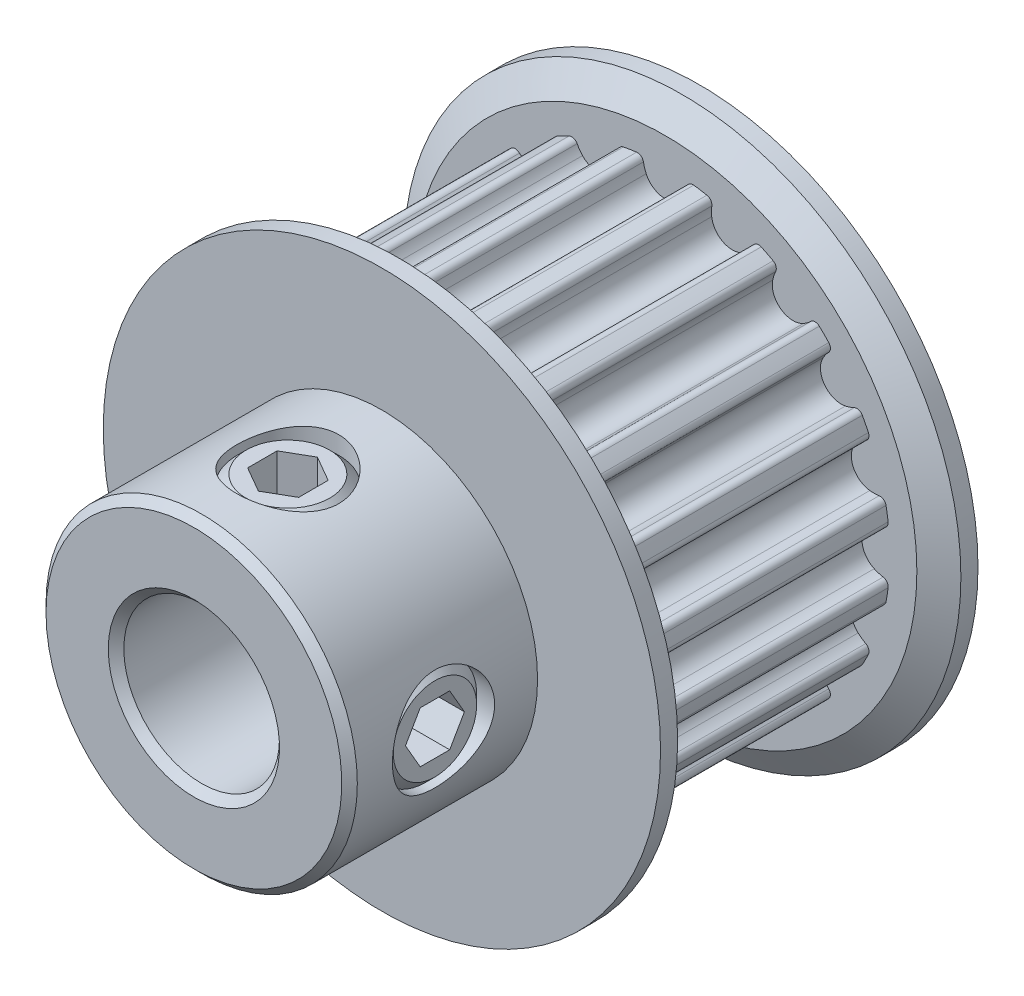
SolidWorks part; units mm, degrees
ref_plane "Front Plane" through (0, 0, 0) normal (0, 0, 1) x (1, 0, 0)
ref_plane "Top Plane" through (0, 0, 0) normal (0, 1, 0) x (1, 0, 0)
ref_plane "Right Plane" through (0, 0, 0) normal (1, 0, 0) x (0, 0, -1)
sketch "Sketch1" plane through (0, 0, 0) normal (0, 0, 1) x (1, 0, 0)
  line L1 (-2.6202, 8.0295) -> (2.6202, 8.0295) construction
  line L4 (0, 0) -> (0, 8.0295) construction
  line L5 (0, 8.0295) -> (0, 13.1511) construction
  line L6 (0, 9.5505) -> (2.9628, 9.0793) construction
  line L7 (2.9628, 9.0793) -> (4.0126, 8.7367) construction
  line L8 (2.9628, 9.0793) -> (2.6202, 8.0295) construction
  line L9 (-2.9628, 9.0793) -> (-2.6202, 8.0295) construction
  line L10 (-2.8446, 8.7171) -> (-3.7091, 11.3665)
  line L11 (-3.7091, 11.3665) -> (3.7091, 11.3665)
  line L12 (3.7091, 11.3665) -> (2.8446, 8.7171)
  circle A0 centre (0, 0) radius 9.5505 construction
  circle A1 centre (0, 0) radius 11.3665 construction
  circle A2 centre (0, 0) radius 9.1695 construction
  arc A3 (-0.7739, 8.5279) -> (0.7739, 8.5279) centre (0, 8.8795) ccw
  arc A4 (-0.7739, 8.5279) -> (-0.8866, 8.891) centre (0.61, 9.1566) cw
  arc A5 (-2.8446, 8.7171) -> (-1.1645, 9.0953) centre (0, 0) cw
  arc A6 (-0.8866, 8.891) -> (-1.1645, 9.0953) centre (-1.1328, 8.8473) ccw
  arc A7 (2.8446, 8.7171) -> (1.1645, 9.0953) centre (0, 0) ccw
  arc A8 (0.8866, 8.891) -> (1.1645, 9.0953) centre (1.1328, 8.8473) cw
  arc A9 (0.7739, 8.5279) -> (0.8866, 8.891) centre (-0.61, 9.1566) ccw
  point P6 (0, 20.9083)
  point P11 (0, 9.5505)
  point P13 (0, 11.3665)
  point P14 (0, 9.1695)
  dimension "D1" = 7.7573
  dimension "D2" = 3.6006
sketch "Sketch2" plane through (0, 0, 0) normal (1, 0, 0) x (0, 0, -1)
  line L0 (-10.31, 3.175) -> (10.31, 3.175)
  line L1 (-10.31, 3.175) -> (-10.31, 6.35)
  line L2 (-10.31, 6.35) -> (-2.64, 6.35)
  line L3 (-2.64, 6.35) -> (-2.64, 11.3665)
  line L4 (-2.64, 11.3665) -> (-1.245, 11.3665) construction
  line L5 (-1.245, 11.3665) -> (-1.245, 9.1695) construction
  line L6 (-1.245, 9.1695) -> (8.915, 9.1695)
  line L7 (8.915, 9.1695) -> (8.915, 11.3665) construction
  line L8 (8.915, 11.3665) -> (10.31, 11.3665) construction
  line L9 (10.31, 11.3665) -> (10.31, 3.175)
  line L10 (-10.31, 0) -> (10.31, 0) construction
  line L11 (9.6125, 11.3665) -> (8.915, 10.268)
  line L12 (-1.245, 10.268) -> (-1.9425, 11.3665)
  line L13 (-2.64, 11.3665) -> (-1.9425, 11.3665)
  line L14 (-1.245, 10.268) -> (-1.245, 9.1695)
  line L15 (8.915, 9.1695) -> (8.915, 10.268)
  line L16 (9.6125, 11.3665) -> (10.31, 11.3665)
  arc A0 (-1.245, 10.268) -> (-1.9425, 11.3665) centre (-2.4588, 10.268) ccw construction
  arc A1 (8.915, 10.268) -> (9.6125, 11.3665) centre (10.1288, 10.268) cw construction
  point P12 (-1.245, 10.268)
  point P14 (-1.9425, 11.3665)
  point P20 (8.915, 10.268)
  point P21 (9.6125, 11.3665)
  point P25 (8.915, 0)
  point P26 (-1.245, 0)
revolve "Revolve1" add sketch "Sketch2" angle 360 mid plane about L10
sketch "Sketch3" plane through (0, 0, 0) normal (0, 0, 1) x (1, 0, 0)
  line L6 (3.7091, 11.3665) -> (-3.7091, 11.3665)
  line L7 (2.8446, 8.7171) -> (3.7091, 11.3665)
  line L8 (-3.7091, 11.3665) -> (-2.8446, 8.7171)
  line L9 (3.7091, 11.3665) -> (-3.7091, 11.3665)
  line L10 (2.8446, 8.7171) -> (3.7091, 11.3665)
  line L11 (-3.7091, 11.3665) -> (-2.8446, 8.7171)
  arc A8 (2.8446, 8.7171) -> (1.1645, 9.0953) centre (0, 0) ccw
  arc A9 (1.1645, 9.0953) -> (0.8866, 8.891) centre (1.1328, 8.8473) ccw
  arc A10 (0.7739, 8.5279) -> (0.8866, 8.891) centre (-0.61, 9.1566) ccw
  arc A11 (-0.7739, 8.5279) -> (0.7739, 8.5279) centre (0, 8.8795) ccw
  arc A12 (-0.8866, 8.891) -> (-0.7739, 8.5279) centre (0.61, 9.1566) ccw
  arc A13 (-0.8866, 8.891) -> (-1.1645, 9.0953) centre (-1.1328, 8.8473) ccw
  arc A14 (-1.1645, 9.0953) -> (-2.8446, 8.7171) centre (0, 0) ccw
  arc A15 (2.8446, 8.7171) -> (1.1645, 9.0953) centre (0, 0) ccw
  arc A16 (1.1645, 9.0953) -> (0.8866, 8.891) centre (1.1328, 8.8473) ccw
  arc A17 (0.7739, 8.5279) -> (0.8866, 8.891) centre (-0.61, 9.1566) ccw
  arc A18 (-0.7739, 8.5279) -> (0.7739, 8.5279) centre (0, 8.8795) ccw
  arc A19 (-0.8866, 8.891) -> (-0.7739, 8.5279) centre (0.61, 9.1566) ccw
  arc A20 (-0.8866, 8.891) -> (-1.1645, 9.0953) centre (-1.1328, 8.8473) ccw
  arc A21 (-1.1645, 9.0953) -> (-2.8446, 8.7171) centre (0, 0) ccw
  dimension "D1" = 0
extrude "Cut-Extrude1" cut sketch "Sketch3" against normal up to vertex (8.915 mm away) from vertex up to point (0, 9.1695, -8.915) starting at point (0, 9.1695, 1.245)
pattern_circular "CirPattern1" count 20 over 360 about axis through (0, 0, 10.31) along (0, 0, 1) of "Cut-Extrude1"
sketch "Sketch4" plane through (0, 0, 0) normal (1, 0, 0) x (0, -1, 0)
  line L0 (0, -2.64) -> (0, -10.31) construction
  line L1 (-6.35, -2.64) -> (6.35, -2.64) construction
  line L2 (-6.35, -10.31) -> (6.35, -10.31) construction
  circle A0 centre (0, -6.475) radius 2.0828
extrude "Cut-Extrude2" cut sketch "Sketch4" along normal through all
ref_plane "Plane1" through (0, 0, 6.475) normal (0, 0, 1) x (1, 0, 0)
sketch "Sketch5" plane through (0, 0, 6.475) normal (0, 0, 1) x (1, 0, 0)
  line L0 (0, 0.1664) -> (0, 6.35) construction
  line L1 (3.175, -1.7018) -> (3.175, 0)
  line L2 (3.556, -2.0828) -> (5.6177, -2.0828)
  line L3 (3.175, 0) -> (6.35, 0) construction
  line L4 (3.175, 0) -> (5.9987, 0)
  line L5 (5.9987, 0) -> (5.9987, -1.7018)
  line L6 (3.556, -2.0828) -> (3.175, -1.7018)
  line L7 (5.9987, -1.7018) -> (5.6177, -2.0828)
  circle A0 centre (0, 0) radius 6.35 construction
  circle A1 centre (0, 0) radius 3.175 construction
  point P2 (3.175, -2.0828)
  point P11 (5.9987, -2.0828)
revolve "Revolve2" add sketch "Sketch5" angle 360 mid plane about L4
sketch "Sketch6" plane through (5.9987, 5.3841, 0) normal (-1, 0, 0) x (0, -1, 0)
  line L1 (5.3841, 7.6775) -> (4.3427, 7.0763)
  line L2 (4.3427, 7.0763) -> (4.3427, 5.8737)
  line L3 (4.3427, 5.8737) -> (5.3841, 5.2725)
  line L4 (5.3841, 5.2725) -> (6.4255, 5.8737)
  line L5 (6.4255, 5.8737) -> (6.4255, 7.0763)
  line L6 (6.4255, 7.0763) -> (5.3841, 7.6775)
  circle A0 centre (5.3841, 6.475) radius 1.0414 construction
  dimension "D1" = 2.0828
extrude "Cut-Extrude3" cut sketch "Sketch6" along normal blind 1.5621
pattern_circular "CirPattern2" count 2 over 90 about axis through (0, 0, 10.31) along (0, 0, 1) of "Cut-Extrude2", "Revolve2", "Cut-Extrude3"
chamfer "Chamfer1" distance 0.3175 angle 45 2 edges at (3.175, 0, 10.31) (6.35, 0, 10.31)
ref_axis "Center Axis 1" through (0, 0, -10.31) along (0, 0, 1)
ref_plane "Contact Plane 1" through (0, 0, 10.31) normal (0, 0, 1) x (1, 0, 0)
ref_plane "Contact Plane 2" through (0, 0, -10.31) normal (0, 0, -1) x (-1, 0, 0)
equation "\"D2@Sketch1\" = \"D1@Sketch1\"/2"
equation "\"D1@Sketch6\" = \"Set Screw@Sketch4\" / 2"
equation "\"D1@Cut-Extrude3\" = \"D1@Sketch6\"*.75"
equation "\"D1@Chamfer1\"=\"Hub Dia@Sketch2\"*.025"
